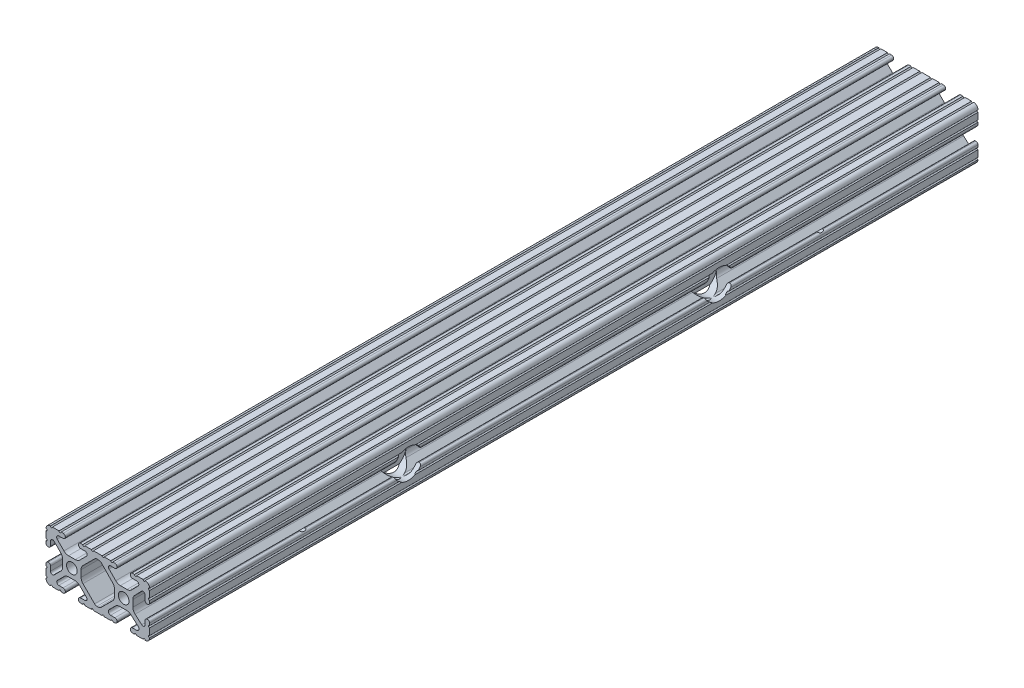
SolidWorks part; units mm, degrees
ref_plane "Front Plane" through (0, 0, 0) normal (0, 0, 1) x (1, 0, 0)
ref_plane "Top Plane" through (0, 0, 0) normal (0, 1, 0) x (1, 0, 0)
ref_plane "Right Plane" through (0, 0, 0) normal (1, 0, 0) x (0, 0, -1)
sketch "Sketch1" plane through (0, 0, 0) normal (0, 0, 1) x (1, 0, 0)
  line L0 (-7.2595, -3.8694) -> (-1.5457, -9.5728)
  line L1 (-8.1915, 1.6223) -> (-8.1915, -1.6223)
  line L2 (-1.504, 9.5765) -> (-7.252, 3.8768)
  line L3 (0.5515, 10.033) -> (-0.3952, 10.033)
  line L4 (7.2829, 3.8459) -> (1.6756, 9.5611)
  line L5 (8.1915, -1.6223) -> (8.1915, 1.6223)
  line L6 (1.5457, -9.5728) -> (7.2595, -3.8694)
  line L7 (-0.4332, -10.033) -> (0.4332, -10.033)
  line L8 (18.0171, 12.7) -> (16.9875, 12.7)
  line L9 (15.9385, 11.651) -> (15.9385, 11.5392)
  line L10 (16.9875, 10.4902) -> (19.1164, 10.4902)
  line L11 (19.8441, 8.7652) -> (16.619, 5.4551)
  line L12 (14.3449, 4.4958) -> (11.0833, 4.4958)
  line L13 (8.817, 5.4472) -> (5.5642, 8.7627)
  line L14 (6.2894, 10.4902) -> (8.4125, 10.4902)
  line L15 (9.4615, 11.5392) -> (9.4615, 11.651)
  line L16 (8.4125, 12.7) -> (7.3829, 12.7)
  line L17 (6.3669, 12.7) -> (3.1496, 12.7)
  line L18 (2.1336, 12.7) -> (-2.1336, 12.7)
  line L19 (-3.1496, 12.7) -> (-6.3669, 12.7)
  line L20 (-7.3829, 12.7) -> (-8.4125, 12.7)
  line L21 (-9.4615, 11.651) -> (-9.4615, 11.5392)
  line L22 (-8.4125, 10.4902) -> (-6.2836, 10.4902)
  line L23 (-5.5326, 8.6661) -> (-8.81, 5.4163)
  line L24 (-11.0455, 4.4958) -> (-14.3545, 4.4958)
  line L25 (-16.59, 5.4163) -> (-19.8674, 8.6661)
  line L26 (-19.1164, 10.4902) -> (-16.9875, 10.4902)
  line L27 (-15.9385, 11.5392) -> (-15.9385, 11.651)
  line L28 (-16.9875, 12.7) -> (-18.0171, 12.7)
  line L29 (-19.0331, 12.7) -> (-22.2504, 12.7)
  line L30 (-25.4, 9.5504) -> (-25.4, 6.3331)
  line L31 (-25.4, 5.3171) -> (-25.4, 4.2375)
  line L32 (-24.401, 3.2385) -> (-24.2392, 3.2385)
  line L33 (-23.1902, 4.2875) -> (-23.1902, 6.3347)
  line L34 (-21.434, 7.0665) -> (-18.148, 3.8082)
  line L35 (-17.2085, 1.5536) -> (-17.2085, -1.6952)
  line L36 (-18.1405, -3.9423) -> (-21.4316, -7.2274)
  line L37 (-23.1902, -6.498) -> (-23.1902, -4.2875)
  line L38 (-24.2392, -3.2385) -> (-24.351, -3.2385)
  line L39 (-25.4, -4.2875) -> (-25.4, -5.3171)
  line L40 (-25.4, -6.3331) -> (-25.4, -9.5504)
  line L41 (-22.2504, -12.7) -> (-19.0331, -12.7)
  line L42 (-18.0171, -12.7) -> (-16.9875, -12.7)
  line L43 (-15.9384, -11.651) -> (-15.9384, -11.5392)
  line L44 (-16.9875, -10.4902) -> (-19.1164, -10.4902)
  line L45 (-19.8341, -8.7551) -> (-16.4966, -5.4237)
  line L46 (-14.2536, -4.4958) -> (-11.1464, -4.4958)
  line L47 (-8.9034, -5.4237) -> (-5.5659, -8.7551)
  line L48 (-6.2836, -10.4902) -> (-8.4125, -10.4902)
  line L49 (-9.4616, -11.5392) -> (-9.4616, -11.651)
  line L50 (-8.4125, -12.7) -> (-7.3829, -12.7)
  line L51 (-6.3669, -12.7) -> (-3.1496, -12.7)
  line L52 (-2.1336, -12.7) -> (2.1336, -12.7)
  line L53 (3.1496, -12.7) -> (6.3669, -12.7)
  line L54 (7.3829, -12.7) -> (8.4125, -12.7)
  line L55 (9.4616, -11.651) -> (9.4616, -11.5392)
  line L56 (8.4125, -10.4902) -> (6.2894, -10.4902)
  line L57 (5.4807, -8.5353) -> (8.5979, -5.4237)
  line L58 (10.8409, -4.4958) -> (14.1026, -4.4958)
  line L59 (16.1879, -5.2766) -> (19.8682, -8.4822)
  line L60 (19.1164, -10.4902) -> (16.9875, -10.4902)
  line L61 (15.9384, -11.5392) -> (15.9384, -11.651)
  line L62 (16.9875, -12.7) -> (18.0171, -12.7)
  line L63 (19.0331, -12.7) -> (22.2504, -12.7)
  line L64 (25.4, -9.5504) -> (25.4, -6.3331)
  line L65 (25.4, -5.3171) -> (25.4, -4.2375)
  line L66 (24.401, -3.2385) -> (24.1892, -3.2385)
  line L67 (23.1902, -4.2375) -> (23.1902, -6.1559)
  line L68 (21.584, -6.8869) -> (18.2982, -4.025)
  line L69 (17.2085, -1.6308) -> (17.2085, 1.6308)
  line L70 (18.1094, 3.8465) -> (21.5263, 7.3534)
  line L71 (23.1902, 6.6769) -> (23.1902, 4.2375)
  line L72 (24.1892, 3.2385) -> (24.401, 3.2385)
  line L73 (25.4, 4.2375) -> (25.4, 5.3171)
  line L74 (25.4, 6.3332) -> (25.4, 9.5504)
  line L75 (22.2504, 12.7) -> (19.0331, 12.7)
  circle A0 centre (-12.7, 0) radius 2.6035
  circle A1 centre (12.7, 0) radius 2.6035
  arc A2 (-1.5457, -9.5728) -> (-0.4332, -10.033) centre (-0.4332, -8.4582) ccw
  arc A3 (-8.1915, -1.6223) -> (-7.2595, -3.8694) centre (-5.0165, -1.6223) ccw
  arc A4 (-7.252, 3.8768) -> (-8.1915, 1.6223) centre (-5.0165, 1.6223) ccw
  arc A5 (-0.3952, 10.033) -> (-1.504, 9.5765) centre (-0.3952, 8.4582) ccw
  arc A6 (1.6756, 9.5611) -> (0.5515, 10.033) centre (0.5515, 8.4582) ccw
  arc A7 (8.1915, 1.6223) -> (7.2829, 3.8459) centre (5.0165, 1.6223) ccw
  arc A8 (7.2595, -3.8694) -> (8.1915, -1.6223) centre (5.0165, -1.6223) ccw
  arc A9 (0.4332, -10.033) -> (1.5457, -9.5728) centre (0.4332, -8.4582) ccw
  arc A10 (18.0171, 12.7) -> (19.0331, 12.7) centre (18.5251, 12.7) ccw
  arc A11 (16.9875, 12.7) -> (15.9385, 11.651) centre (16.9875, 11.651) ccw
  arc A12 (15.9385, 11.5392) -> (16.9875, 10.4902) centre (16.9875, 11.5392) ccw
  arc A13 (19.8441, 8.7652) -> (19.1164, 10.4902) centre (19.1164, 9.4742) ccw
  arc A14 (14.3449, 4.4958) -> (16.619, 5.4551) centre (14.3449, 7.6708) ccw
  arc A15 (8.817, 5.4472) -> (11.0833, 4.4958) centre (11.0833, 7.6708) ccw
  arc A16 (6.2894, 10.4902) -> (5.5642, 8.7627) centre (6.2894, 9.4742) ccw
  arc A17 (8.4125, 10.4902) -> (9.4615, 11.5392) centre (8.4125, 11.5392) ccw
  arc A18 (9.4615, 11.651) -> (8.4125, 12.7) centre (8.4125, 11.651) ccw
  arc A19 (6.3669, 12.7) -> (7.3829, 12.7) centre (6.8749, 12.7) ccw
  arc A20 (2.1336, 12.7) -> (3.1496, 12.7) centre (2.6416, 12.7) ccw
  arc A21 (-3.1496, 12.7) -> (-2.1336, 12.7) centre (-2.6416, 12.7) ccw
  arc A22 (-7.3829, 12.7) -> (-6.3669, 12.7) centre (-6.8749, 12.7) ccw
  arc A23 (-8.4125, 12.7) -> (-9.4615, 11.651) centre (-8.4125, 11.651) ccw
  arc A24 (-9.4615, 11.5392) -> (-8.4125, 10.4902) centre (-8.4125, 11.5392) ccw
  arc A25 (-5.5326, 8.6661) -> (-6.2836, 10.4902) centre (-6.2836, 9.4235) ccw
  arc A26 (-11.0455, 4.4958) -> (-8.81, 5.4163) centre (-11.0455, 7.6708) ccw
  arc A27 (-16.59, 5.4163) -> (-14.3545, 4.4958) centre (-14.3545, 7.6708) ccw
  arc A28 (-19.1164, 10.4902) -> (-19.8674, 8.6661) centre (-19.1164, 9.4235) ccw
  arc A29 (-16.9875, 10.4902) -> (-15.9385, 11.5392) centre (-16.9875, 11.5392) ccw
  arc A30 (-15.9385, 11.651) -> (-16.9875, 12.7) centre (-16.9875, 11.651) ccw
  arc A31 (-19.0331, 12.7) -> (-18.0171, 12.7) centre (-18.5251, 12.7) ccw
  arc A32 (-23.2664, 12.6998) -> (-22.2504, 12.7) centre (-22.7584, 12.7) ccw
  arc A33 (-23.2664, 12.6998) -> (-25.3998, 10.5664) centre (-23.2918, 10.5918) ccw
  arc A34 (-25.4, 9.5504) -> (-25.3998, 10.5664) centre (-25.4, 10.0584) ccw
  arc A35 (-25.4, 5.3171) -> (-25.4, 6.3331) centre (-25.4, 5.8251) ccw
  arc A36 (-25.4, 4.2375) -> (-24.401, 3.2385) centre (-24.401, 4.2375) ccw
  arc A37 (-24.2392, 3.2385) -> (-23.1902, 4.2875) centre (-24.2392, 4.2875) ccw
  arc A38 (-21.434, 7.0665) -> (-23.1902, 6.3347) centre (-22.1596, 6.3347) ccw
  arc A39 (-17.2085, 1.5536) -> (-18.148, 3.8082) centre (-20.3835, 1.5536) ccw
  arc A40 (-18.1405, -3.9423) -> (-17.2085, -1.6952) centre (-20.3835, -1.6952) ccw
  arc A41 (-23.1902, -6.498) -> (-21.4316, -7.2274) centre (-22.1596, -6.498) ccw
  arc A42 (-23.1902, -4.2875) -> (-24.2392, -3.2385) centre (-24.2392, -4.2875) ccw
  arc A43 (-24.351, -3.2385) -> (-25.4, -4.2875) centre (-24.351, -4.2875) ccw
  arc A44 (-25.4, -6.3331) -> (-25.4, -5.3171) centre (-25.4, -5.8251) ccw
  arc A45 (-25.3998, -10.5664) -> (-25.4, -9.5504) centre (-25.4, -10.0584) ccw
  arc A46 (-25.3998, -10.5664) -> (-23.2664, -12.6998) centre (-23.2918, -10.5918) ccw
  arc A47 (-22.2504, -12.7) -> (-23.2664, -12.6998) centre (-22.7584, -12.7) ccw
  arc A48 (-18.0171, -12.7) -> (-19.0331, -12.7) centre (-18.5251, -12.7) ccw
  arc A49 (-16.9875, -12.7) -> (-15.9384, -11.651) centre (-16.9875, -11.651) ccw
  arc A50 (-15.9384, -11.5392) -> (-16.9875, -10.4902) centre (-16.9875, -11.5392) ccw
  arc A51 (-19.8341, -8.7551) -> (-19.1164, -10.4902) centre (-19.1164, -9.4742) ccw
  arc A52 (-14.2536, -4.4958) -> (-16.4966, -5.4237) centre (-14.2536, -7.6708) ccw
  arc A53 (-8.9034, -5.4237) -> (-11.1464, -4.4958) centre (-11.1464, -7.6708) ccw
  arc A54 (-6.2836, -10.4902) -> (-5.5659, -8.7551) centre (-6.2836, -9.4742) ccw
  arc A55 (-8.4125, -10.4902) -> (-9.4616, -11.5392) centre (-8.4125, -11.5392) ccw
  arc A56 (-9.4616, -11.651) -> (-8.4125, -12.7) centre (-8.4125, -11.651) ccw
  arc A57 (-6.3669, -12.7) -> (-7.3829, -12.7) centre (-6.8749, -12.7) ccw
  arc A58 (-2.1336, -12.7) -> (-3.1496, -12.7) centre (-2.6416, -12.7) ccw
  arc A59 (3.1496, -12.7) -> (2.1336, -12.7) centre (2.6416, -12.7) ccw
  arc A60 (7.3829, -12.7) -> (6.3669, -12.7) centre (6.8749, -12.7) ccw
  arc A61 (8.4125, -12.7) -> (9.4616, -11.651) centre (8.4125, -11.651) ccw
  arc A62 (9.4616, -11.5392) -> (8.4125, -10.4902) centre (8.4125, -11.5392) ccw
  arc A63 (5.4807, -8.5353) -> (6.2894, -10.4902) centre (6.2894, -9.3455) ccw
  arc A64 (10.8409, -4.4958) -> (8.5979, -5.4237) centre (10.8409, -7.6708) ccw
  arc A65 (16.1879, -5.2766) -> (14.1026, -4.4958) centre (14.1026, -7.6708) ccw
  arc A66 (19.1164, -10.4902) -> (19.8682, -8.4822) centre (19.1164, -9.3455) ccw
  arc A67 (16.9875, -10.4902) -> (15.9384, -11.5392) centre (16.9875, -11.5392) ccw
  arc A68 (15.9384, -11.651) -> (16.9875, -12.7) centre (16.9875, -11.651) ccw
  arc A69 (19.0331, -12.7) -> (18.0171, -12.7) centre (18.5251, -12.7) ccw
  arc A70 (23.2664, -12.6998) -> (22.2504, -12.7) centre (22.7584, -12.7) ccw
  arc A71 (23.2664, -12.6998) -> (25.3998, -10.5664) centre (23.2918, -10.5918) ccw
  arc A72 (25.4, -9.5504) -> (25.3998, -10.5664) centre (25.4, -10.0584) ccw
  arc A73 (25.4, -5.3171) -> (25.4, -6.3331) centre (25.4, -5.8251) ccw
  arc A74 (25.4, -4.2375) -> (24.401, -3.2385) centre (24.401, -4.2375) ccw
  arc A75 (24.1892, -3.2385) -> (23.1902, -4.2375) centre (24.1892, -4.2375) ccw
  arc A76 (21.584, -6.8869) -> (23.1902, -6.1559) centre (22.2207, -6.1559) ccw
  arc A77 (17.2085, -1.6308) -> (18.2982, -4.025) centre (20.3835, -1.6308) ccw
  arc A78 (18.1094, 3.8465) -> (17.2085, 1.6308) centre (20.3835, 1.6308) ccw
  arc A79 (23.1902, 6.6769) -> (21.5263, 7.3534) centre (22.2207, 6.6769) ccw
  arc A80 (23.1902, 4.2375) -> (24.1892, 3.2385) centre (24.1892, 4.2375) ccw
  arc A81 (24.401, 3.2385) -> (25.4, 4.2375) centre (24.401, 4.2375) ccw
  arc A82 (25.4, 6.3332) -> (25.4, 5.3171) centre (25.4, 5.8251) ccw
  arc A83 (25.3998, 10.5664) -> (25.4, 9.5504) centre (25.4, 10.0584) ccw
  arc A84 (25.3998, 10.5664) -> (23.2664, 12.6998) centre (23.2918, 10.5918) ccw
  arc A85 (22.2504, 12.7) -> (23.2664, 12.6998) centre (22.7584, 12.7) ccw
  point P248 (0, 10.033)
extrude "Boss-Extrude1" add sketch "Sketch1" along normal mid plane 406.4
sketch "Sketch2" plane through (25.4, 0, 0) normal (1, 0, 0) x (0, 0, -1)
  line L0 (0, 0) -> (-203.2, 0) construction
  line L1 (-203.2, -1.6308) -> (-203.2, 1.6308) construction
  circle A0 centre (-127, 0) radius 3.5
  dimension "D2" = 7
  dimension "D1" = 76.2
extrude "Cut-Extrude1" cut sketch "Sketch2" against normal through all
ref_plane "Plane1" through (0, 0, 0) normal (0, 0, 1) x (1, 0, 0)
mirror "Mirror1" about plane through (0, 0, 0) normal (0, 0, 1) of "Cut-Extrude1"
hole_wizard "CBORE for 1/4 Binding Head Machine Screw1" positions "Sketch4" profile "Sketch6" counterbore size "1/4" standard "ANSI Inch" end condition through all
sketch "Sketch4" plane through (25.4, 0, 0) normal (1, 0, 0) x (0, 0, -1)
  line L0 (-76.2, 0) -> (76.2, 0) construction
  point P0 (-76.2, 0)
  point P2 (76.2, 0)
  point P9 (0, 0)
  dimension "D1" = 152.4
sketch "Sketch6" plane through (25.4, 0, 76.2) normal (0, 1, 0) x (0, 0, -1)
  line L0 (0, 0) -> (0, 50.8)
  line L1 (0, 50.8) -> (3.3782, 50.8)
  line L3 (3.3782, 50.8) -> (3.3782, 8.255)
  line L4 (3.3782, 8.255) -> (7.1437, 8.255)
  line L5 (7.1437, 8.255) -> (7.1437, 0)
  line L7 (7.1437, 0) -> (0, 0)
  line L11 (0, -6.35) -> (0, 107.95) construction
  dimension "Thru Hole Dia." = 6.7564
  dimension "Thru Hole Depth" = 50.8
  dimension "C'Bore Dia." = 14.2875
  dimension "C'Bore Depth" = 8.255
